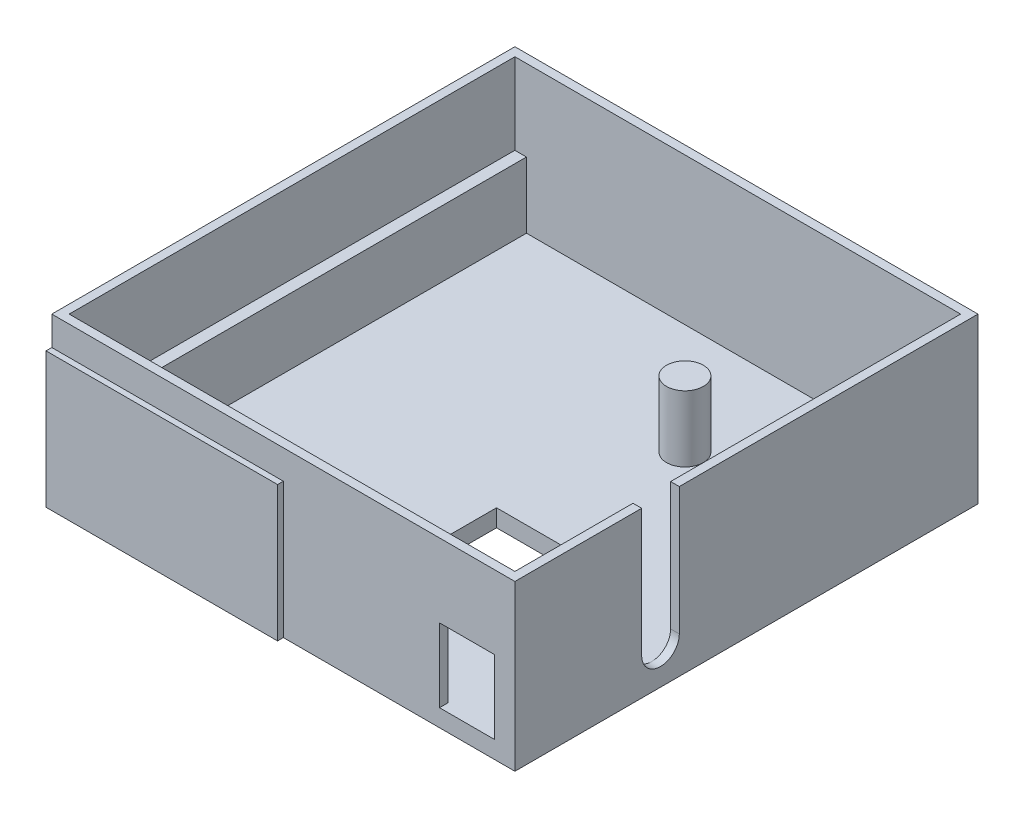
SolidWorks part; units mm, degrees
ref_plane "Front Plane" through (0, 0, 0) normal (0, 0, 1) x (1, 0, 0)
ref_plane "Top Plane" through (0, 0, 0) normal (0, 1, 0) x (1, 0, 0)
ref_plane "Right Plane" through (0, 0, 0) normal (1, 0, 0) x (0, 0, -1)
sketch "Sketch1" plane through (0, 0, 0) normal (0, 1, 0) x (1, 0, 0)
  line L1 (-40, -40) -> (40, -40)
  line L2 (-40, -40) -> (-40, 40)
  line L3 (-40, 40) -> (40, 40)
  line L4 (40, -40) -> (40, 40)
  line L5 (-40, -40) -> (40, 40) construction
  line L6 (-40, 40) -> (40, -40) construction
  point P0 (0, 0)
  dimension "D1" = 80
extrude "Boss-Extrude1" add sketch "Sketch1" along normal blind 3
sketch "Sketch2" plane through (0, 3, 0) normal (0, 1, 0) x (1, 0, 0)
  line L1 (-40, -40) -> (40, -40)
  line L2 (-40, -40) -> (-40, 40)
  line L3 (-40, 40) -> (40, 40)
  line L4 (40, -40) -> (40, 40)
  line L5 (-40, -40) -> (40, 40) construction
  line L6 (-40, 40) -> (40, -40) construction
  line L7 (-38.5, -38.5) -> (38.5, -38.5)
  line L8 (-38.5, -38.5) -> (-38.5, 38.5)
  line L9 (-38.5, 38.5) -> (38.5, 38.5)
  line L10 (38.5, -38.5) -> (38.5, 38.5)
  line L11 (-38.5, -38.5) -> (38.5, 38.5) construction
  line L12 (-38.5, 38.5) -> (38.5, -38.5) construction
  point P0 (0, 0)
  point P7 (0, 0)
  dimension "D1" = 77
  dimension "D2" = 77
extrude "Boss-Extrude2" add sketch "Sketch2" along normal blind 25.4
sketch "Sketch3" plane through (40, 0, 0) normal (1, 0, 0) x (0, 0, -1)
  line L0 (-38.5, 28.4) -> (-38.5, 3) construction
  line L1 (-40, 0) -> (40, 0) construction
  line L2 (-11.6, 6.35) -> (-11.6, 28.4)
  line L3 (-40, 28.4) -> (40, 28.4) construction
  line L4 (-11.6, 28.4) -> (-18.1, 28.4)
  line L5 (-18.1, 28.4) -> (-18.1, 6.35)
  circle A0 centre (-14.85, 6.35) radius 3.25
  line M3 (40, 28.4) -> (-40, 28.4)
  dimension "D3" = 6.5
  dimension "D1" = 23.65
  dimension "D2" = 6.35
extrude "Cut-Extrude2" cut sketch "Sketch3" against normal up to surface (1.5 mm away) contours A0 | A0 L2 L5 M3 region at (40, 18.6378, 14.85) region at (40, 6.35, 14.85) up to face at (38.5, 15.7, 0)
sketch "Sketch5" plane through (0, 0, 40) normal (0, 0, 1) x (1, 0, 0)
  line L1 (26.975, 3) -> (36.5, 3)
  line L2 (26.975, 3) -> (26.975, 15.7)
  line L3 (26.975, 15.7) -> (36.5, 15.7)
  line L4 (36.5, 3) -> (36.5, 15.7)
  line L5 (26.975, 3) -> (36.5, 15.7) construction
  line L6 (26.975, 15.7) -> (36.5, 3) construction
  line L7 (-40, 0) -> (40, 0) construction
  line L15 (38.5, 28.4) -> (38.5, 3) construction
  point P0 (31.7375, 9.35)
  dimension "D1" = 12.7
  dimension "D2" = 9.525
  dimension "D3" = 2
  dimension "D4" = 3
extrude "Cut-Extrude3" cut sketch "Sketch5" against normal blind 19.05
sketch "Sketch6" plane through (0, 3, 0) normal (0, 1, 0) x (1, 0, 0)
  line L0 (38.5, -38.5) -> (38.5, 38.5) construction
  line L1 (38.5, 38.5) -> (-38.5, 38.5) construction
  line L3 (-38.5, 38.5) -> (-36.5, 38.5)
  line L4 (-38.5, 38.5) -> (-38.5, -26.5)
  line L5 (-38.5, -26.5) -> (-36.5, -26.5)
  line L6 (-36.5, 38.5) -> (-36.5, -26.5)
  circle A0 centre (9.925, 19.45) radius 3.175
  point P13 (0, 0)
  dimension "D3" = 6.35
  dimension "D1" = 28.575
  dimension "D2" = 19.05
  dimension "D4" = 2
  dimension "D5" = 65
extrude "Boss-Extrude3" add sketch "Sketch6" along normal blind 11.4
sketch "Sketch7" plane through (0, 3, 0) normal (0, 1, 0) x (1, 0, 0)
  line L0 (-38.5, -38.5) -> (26.975, -38.5) construction
  line L1 (1.9875, -17.8625) -> (14.6875, -17.8625)
  line L2 (1.9875, -17.8625) -> (1.9875, -5.1625)
  line L3 (1.9875, -5.1625) -> (14.6875, -5.1625)
  line L4 (14.6875, -17.8625) -> (14.6875, -5.1625)
  line L5 (1.9875, -17.8625) -> (14.6875, -5.1625) construction
  line L6 (1.9875, -5.1625) -> (14.6875, -17.8625) construction
  line L7 (38.5, -38.5) -> (38.5, 38.5) construction
  point P0 (8.3375, -11.5125)
  dimension "D1" = 12.7
  dimension "D2" = 12.7
  dimension "D3" = 26.9875
  dimension "D4" = 30.1625
extrude "Cut-Extrude5" cut sketch "Sketch7" against normal blind 26
sketch "Sketch8" plane through (0, 0, 40) normal (0, 0, 1) x (1, 0, 0)
  line L1 (-38.5, 3) -> (-18.5, 3)
  line L2 (-38.5, 3) -> (-38.5, 22.4)
  line L4 (-18.5, 3) -> (-18.5, 22.4)
  line L5 (-38.5, 3) -> (26.975, 3) construction
  line L6 (-38.5, 28.4) -> (-38.5, 3) construction
  line L7 (-38.5, 22.4) -> (-18.5, 22.4)
  line L8 (-40, 28.4) -> (40, 28.4) construction
  point P12 (0, 0)
  dimension "D1" = 20
  dimension "D2" = 6
extrude "Cut-Extrude6" cut sketch "Sketch8" against normal up to surface (1.5 mm away) up to face at (15.8687, 12.525, 38.5)
sketch "Sketch9" plane through (0, 0, 0) normal (0, 1, 0) x (1, 0, 0)
  line L1 (-40, -40) -> (0, -40)
  line L2 (-40, -40) -> (-40, -41)
  line L3 (-40, -41) -> (0, -41)
  line L4 (0, -40) -> (0, -41)
  dimension "D1" = 40
  dimension "D2" = 1
extrude "Boss-Extrude4" add sketch "Sketch9" along normal offset from surface (23.4 mm away) 5 up to face at (13.0833, 28.4, 4.95)
